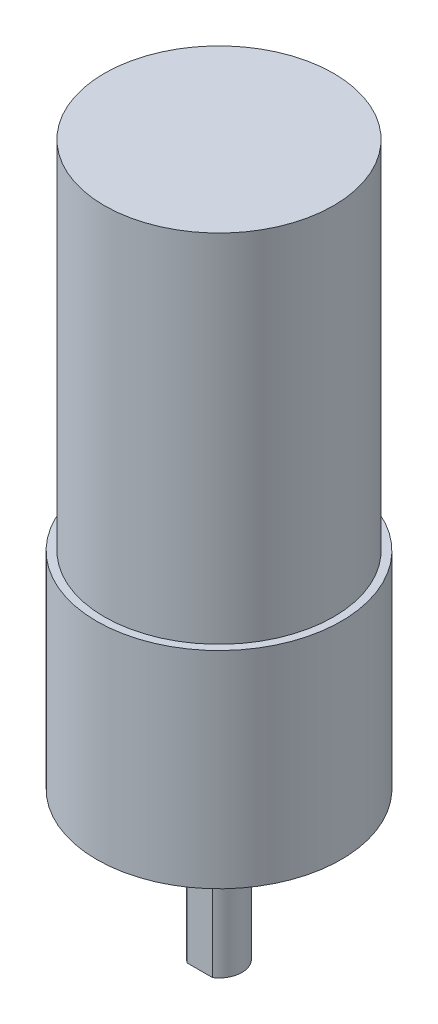
SolidWorks part; units mm, degrees
ref_plane "Plan de face" through (0, 0, 0) normal (0, 0, 1) x (1, 0, 0)
ref_plane "Plan de dessus" through (0, 0, 0) normal (0, 1, 0) x (1, 0, 0)
ref_plane "Plan de droite" through (0, 0, 0) normal (1, 0, 0) x (0, 0, -1)
sketch "Esquisse1" plane through (0, 0, 0) normal (0, 1, 0) x (1, 0, 0)
  circle A0 centre (0, 0) radius 16
  dimension "D1" = 32
extrude "Extrusion1" add sketch "Esquisse1" along normal blind 27
sketch "Esquisse2" plane through (0, 0, 0) normal (0, -1, 0) x (1, 0, 0)
  line L0 (-9, 4.3589) -> (-9, -4.3589)
  line L2 (9, 4.3589) -> (9, -4.3589)
  arc A0 (9, -4.3589) -> (-9, -4.3589) centre (0, 0) cw
  arc A1 (-9, 4.3589) -> (9, 4.3589) centre (0, 0) cw
  dimension "D1" = 9
  dimension "D5" = 10
  dimension "D3" = 10
  dimension "D2" = 18
extrude "Extrusion2" add sketch "Esquisse2" along normal blind 3
sketch "Esquisse3" plane through (0, -3, 0) normal (0, -1, 0) x (1, 0, 0)
  circle A0 centre (0, 0) radius 3
  dimension "D1" = 6
extrude "Extrusion3" add sketch "Esquisse3" along normal blind 16.3
sketch "Esquisse4" plane through (0, -19.3, 0) normal (0, -1, 0) x (1, 0, 0)
  line L0 (0, 0) -> (3, 0) construction
  line L1 (-1.6583, 2.5) -> (1.6583, 2.5)
  circle A0 centre (0, 0) radius 3 construction
  arc A1 (-1.6583, 2.5) -> (1.6583, 2.5) centre (0, 0) cw
  circle M1 centre (0, 0) radius 3
  dimension "D1" = 2.5
extrude "Enlèv. mat.-Extru.1" cut sketch "Esquisse4" against normal blind 12 contours L1 M1 region at (0, -19.3, 2.7015)
sketch "Esquisse5" plane through (0, 27, 0) normal (0, 1, 0) x (-1, 0, 0)
  circle A0 centre (0, 0) radius 15
  dimension "D1" = 30
extrude "Extrusion4" add sketch "Esquisse5" along normal blind 46.6
sketch "Esquisse6" plane through (0, 0, 0) normal (0, -1, 0) x (1, 0, 0)
  line L0 (-16, 0) -> (16, 0) construction
  line L1 (0, 0) -> (11.3137, 11.3137) construction
  line L2 (0, 16) -> (0, -16) construction
  circle A0 centre (0, 0) radius 16 construction
  circle A1 centre (9.1924, 9.1924) radius 1.5
  circle A2 centre (-9.1924, 9.1924) radius 1.5
  circle A3 centre (9.1924, -9.1924) radius 1.5
  circle A4 centre (-9.1924, -9.1924) radius 1.5
  dimension "D3" = 3
  dimension "D1" = 45
  dimension "D2" = 13
extrude "Enlèv. mat.-Extru.2" cut sketch "Esquisse6" against normal blind 5.5
